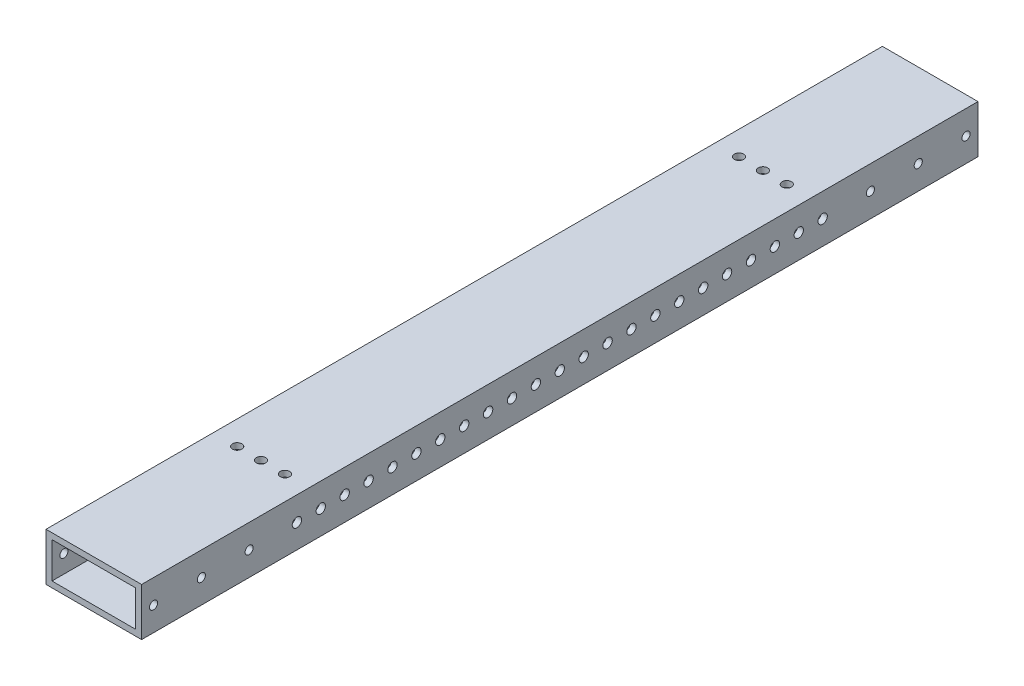
SolidWorks part; units mm, degrees
material "6061-T6 (SS)"
ref_plane "Front Plane" through (0, 0, 0) normal (0, 0, 1) x (1, 0, 0)
ref_plane "Top Plane" through (0, 0, 0) normal (0, 1, 0) x (1, 0, 0)
ref_plane "Right Plane" through (0, 0, 0) normal (1, 0, 0) x (0, 0, -1)
sketch "Sketch1" plane through (0, 0, 0) normal (0, 0, 1) x (1, 0, 0)
  line L0 (-22.225, 9.525) -> (22.225, 9.525)
  line L1 (-25.4, 12.7) -> (25.4, 12.7)
  line L2 (-25.4, 12.7) -> (-25.4, -12.7)
  line L3 (-25.4, -12.7) -> (25.4, -12.7)
  line L4 (25.4, 12.7) -> (25.4, -12.7)
  line L5 (22.225, 9.525) -> (22.225, -9.525)
  line L6 (-22.225, -9.525) -> (22.225, -9.525)
  line L7 (-22.225, 9.525) -> (-22.225, -9.525)
  line L8 (-25.4, 12.7) -> (25.4, -12.7) construction
  line L9 (25.4, 12.7) -> (-25.4, -12.7) construction
  point P5 (0, 0)
  dimension "D1" = 50.8
  dimension "D2" = 25.4
  dimension "D3" = 3.175
extrude "Boss-Extrude1" add sketch "Sketch1" along normal mid plane 444.5
sketch "Sketch3" plane through (25.4, 0, 0) normal (1, 0, 0) x (0, 0, -1)
  line L0 (-222.25, -12.7) -> (-222.25, 12.7) construction
  line L1 (-222.25, 12.7) -> (222.25, 12.7) construction
  line L2 (222.25, -12.7) -> (222.25, 12.7) construction
  circle A0 centre (-215.9, 0) radius 2.1527
  circle A1 centre (-190.5, 0) radius 2.1527
  circle A2 centre (-165.1, 0) radius 2.1527
  circle A3 centre (215.9, 0) radius 2.159
  circle A4 centre (190.5, 0) radius 2.159
  circle A5 centre (165.1, 0) radius 2.159
  dimension "D2" = 4.3053
  dimension "D9" = 4.318
  dimension "D1" = 6.35
  dimension "D3" = 12.7
  dimension "D4" = 31.75
  dimension "D5" = 12.7
  dimension "D6" = 57.15
  dimension "D7" = 12.7
  dimension "D8" = 6.35
  dimension "D10" = 12.7
  dimension "D11" = 31.75
  dimension "D12" = 57.15
  dimension "D13" = 12.7
  dimension "D14" = 12.7
extrude "Cut-Extrude2" cut sketch "Sketch3" against normal through all
sketch "Sketch4" plane through (25.4, 0, 0) normal (1, 0, 0) x (0, 0, -1)
  line L1 (-222.25, -12.7) -> (-222.25, 12.7) construction
  line L2 (-222.25, -12.7) -> (222.25, -12.7) construction
  circle A2 centre (-215.9, 0) radius 2.4892 construction
  circle A3 centre (-203.2, 0) radius 2.4892 construction
  circle A16 centre (-190.5, 0) radius 2.4892 construction
  circle A17 centre (-177.8, 0) radius 2.4892 construction
  circle A18 centre (-165.1, 0) radius 2.4892 construction
  circle A35 centre (-152.4, 0) radius 2.4892
  circle A36 centre (-139.7, 0) radius 2.4892
  circle A37 centre (-127, 0) radius 2.4892
  circle A38 centre (-114.3, 0) radius 2.4892
  circle A39 centre (-101.6, 0) radius 2.4892
  circle A40 centre (-88.9, 0) radius 2.4892
  circle A41 centre (-76.2, 0) radius 2.4892
  circle A42 centre (-63.5, 0) radius 2.4892
  circle A43 centre (-50.8, 0) radius 2.4892
  circle A44 centre (-38.1, 0) radius 2.4892
  circle A45 centre (-25.4, 0) radius 2.4892
  circle A46 centre (-12.7, 0) radius 2.4892
  circle A47 centre (0, 0) radius 2.4892
  circle A48 centre (12.7, 0) radius 2.4892
  circle A49 centre (25.4, 0) radius 2.4892
  circle A50 centre (38.1, 0) radius 2.4892
  circle A51 centre (50.8, 0) radius 2.4892
  circle A52 centre (63.5, 0) radius 2.4892
  circle A53 centre (76.2, 0) radius 2.4892
  circle A54 centre (88.9, 0) radius 2.4892
  circle A55 centre (101.6, 0) radius 2.4892
  circle A56 centre (114.3, 0) radius 2.4892
  circle A57 centre (127, 0) radius 2.4892
  circle A58 centre (139.7, 0) radius 2.4892
  circle A59 centre (152.4, 0) radius 2.4892
  circle A60 centre (165.1, 0) radius 2.4892 construction
  circle A61 centre (177.8, 0) radius 2.4892 construction
  circle A62 centre (190.5, 0) radius 2.4892 construction
  circle A63 centre (203.2, 0) radius 2.4892 construction
  dimension "D2" = 4.9784
  dimension "D1" = 6.35
  dimension "D3" = 12.7
  dimension "D4" = 12.7
  dimension "D5" = 34
extrude "Cut-Extrude3" cut sketch "Sketch4" against normal through all contours A36 | A37 | A38 | A39 | A40 | A41 | A42 | A43 | A44 | A45 | A46 | A47 | A48 | A49 | A50 | A51 | A52 | A53 | A54 | A55 | A56 | A57 | A58 region at (25.4, 0, 139.7) region at (25.4, 0, 127) region at (25.4, 0, 114.3) region at (25.4, 0, 101.6) region at (25.4, 0, 88.9) region at (25.4, 0, 76.2) region at (25.4, 0, 63.5) region at (25.4, 0, 50.8) region at (25.4, 0, 38.1) region at (25.4, 0, 25.4) region at (25.4, 0, 12.7) region at (25.4, 0, 0) region at (25.4, 0, -12.7) region at (25.4, 0, -25.4) region at (25.4, 0, -38.1) region at (25.4, 0, -50.8) region at (25.4, 0, -63.5) region at (25.4, 0, -76.2) region at (25.4, 0, -88.9) region at (25.4, 0, -101.6) region at (25.4, 0, -114.3) region at (25.4, 0, -127) region at (25.4, 0, -139.7)
sketch "Sketch5" plane through (0, -12.7, 0) normal (0, -1, 0) x (1, 0, 0)
  line L0 (-25.4, 0) -> (25.4, 0) construction
  line L4 (25.4, 222.25) -> (25.4, -222.25) construction
  line L5 (-25.4, 222.25) -> (-25.4, -222.25) construction
  line L6 (-25.4, 222.25) -> (25.4, 222.25) construction
  circle A0 centre (-12.7, 133.35) radius 2.4892
  circle A1 centre (0, 133.35) radius 2.4892
  circle A2 centre (12.7, 133.35) radius 2.4892
  circle A3 centre (12.7, -133.35) radius 2.4892
  circle A4 centre (0, -133.35) radius 2.4892
  circle A5 centre (-12.7, -133.35) radius 2.4892
  dimension "D1" = 4.9784
  dimension "D3" = 12.7
  dimension "D2" = 88.9
  dimension "D5" = 12.7
  dimension "D4" = 12.7
extrude "Cut-Extrude4" cut sketch "Sketch5" against normal through all
